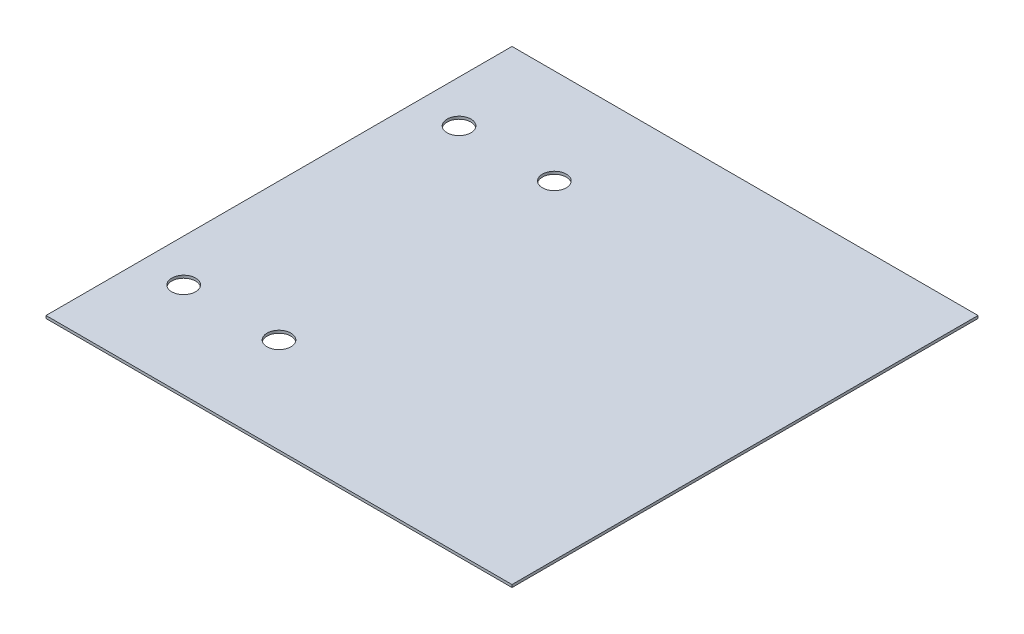
SolidWorks part; units mm, degrees
ref_plane "Front Plane" through (0, 0, 0) normal (0, 0, 1) x (1, 0, 0)
ref_plane "Top Plane" through (0, 0, 0) normal (0, 1, 0) x (1, 0, 0)
ref_plane "Right Plane" through (0, 0, 0) normal (1, 0, 0) x (0, 0, -1)
sketch "Sketch1" plane through (0, 0, 0) normal (0, 1, 0) x (1, 0, 0)
  line L1 (0, 0) -> (558.8, 0)
  line L2 (0, 0) -> (0, 558.8)
  line L3 (0, 558.8) -> (558.8, 558.8)
  line L4 (558.8, 0) -> (558.8, 558.8)
  dimension "D1" = 558.8
  dimension "D2" = 558.8
extrude "Boss-Extrude1" add sketch "Sketch1" along normal blind 3.175
sketch "Sketch2" plane through (0, 3.175, 0) normal (0, 1, 0) x (1, 0, 0)
  line L0 (107.95, 444.5) -> (107.95, 558.8) construction
  line L1 (50.8, 444.5) -> (165.1, 444.5) construction
  line L3 (50.8, 114.3) -> (165.1, 114.3) construction
  line L5 (558.8, 558.8) -> (0, 558.8) construction
  line L6 (107.95, 114.3) -> (107.95, 0) construction
  line L7 (0, 0) -> (558.8, 0) construction
  line L9 (0, 558.8) -> (0, 0) construction
  circle A0 centre (50.8, 444.5) radius 14.2875
  circle A1 centre (165.1, 444.5) radius 14.2875
  circle A2 centre (50.8, 114.3) radius 14.2875
  circle A3 centre (165.1, 114.3) radius 14.2875
  dimension "D1" = 28.575
  dimension "D2" = 28.575
  dimension "D3" = 28.575
  dimension "D4" = 28.575
  dimension "D5" = 114.3
  dimension "D6" = 114.3
  dimension "D7" = 330.2
  dimension "D8" = 50.8
extrude "Cut-Extrude1" cut sketch "Sketch2" against normal blind 3.175
